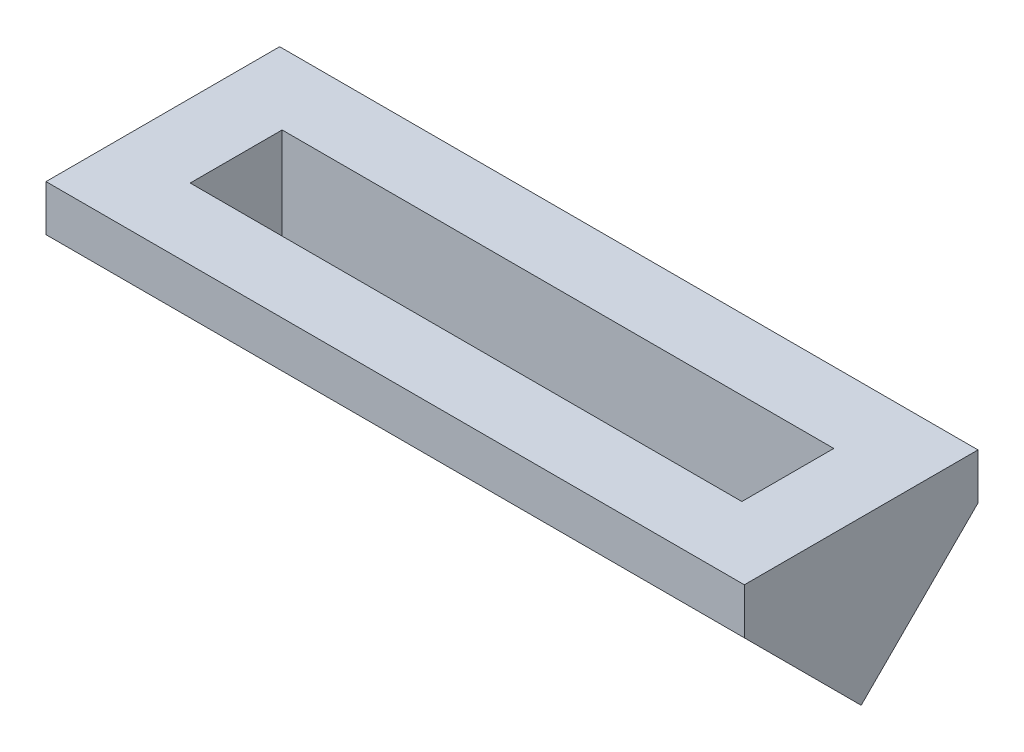
SolidWorks part; units mm, degrees
ref_plane "Front Plane" through (0, 0, 0) normal (0, 0, 1) x (1, 0, 0)
ref_plane "Top Plane" through (0, 0, 0) normal (0, 1, 0) x (1, 0, 0)
ref_plane "Right Plane" through (0, 0, 0) normal (1, 0, 0) x (0, 0, -1)
sketch "Sketch1" plane through (0, 0, 0) normal (0, 1, 0) x (1, 0, 0)
  line L1 (-76.2, -12.7) -> (76.2, -12.7)
  line L2 (-76.2, -12.7) -> (-76.2, 12.7)
  line L3 (-76.2, 12.7) -> (76.2, 12.7)
  line L4 (76.2, -12.7) -> (76.2, 12.7)
  line L5 (-76.2, -12.7) -> (76.2, 12.7) construction
  line L6 (-76.2, 12.7) -> (76.2, -12.7) construction
  line L7 (-96.4606, -32.2717) -> (96.4606, -32.2717)
  line L8 (-96.4606, -32.2717) -> (-96.4606, 32.2717)
  line L9 (-96.4606, 32.2717) -> (96.4606, 32.2717)
  line L10 (96.4606, -32.2717) -> (96.4606, 32.2717)
  line L11 (-96.4606, -32.2717) -> (96.4606, 32.2717) construction
  line L12 (-96.4606, 32.2717) -> (96.4606, -32.2717) construction
  point P0 (0, 0)
  point P6 (0, 0)
  dimension "D1" = 25.4
  dimension "D2" = 152.4
  dimension "D3" = 64.5434
extrude "Boss-Extrude4" add sketch "Sketch1" against normal blind 50.8 contours L7 L10 L9 L8 L4 L1 L2 L3 | L1 L4 L3 L2 | L8 L7 L10 L9 region at (0, 0, 0) region at (-94.4262, 0, 0)
chamfer "Chamfer2" distance 38.1 angle 45 2 edges at (0, -50.8, 32.2717) (0, -50.8, -32.2717)
extrude "Cut-Extrude1" cut sketch "Sketch1<5>" against normal blind 35.56 contours L1 L4 L3 L2 region at (0, 0, 0)
sketch "Sketch1<5>" plane through (0, 0, 0) normal (0, 1, 0) x (1, 0, 0) same geometry as "Sketch1"
